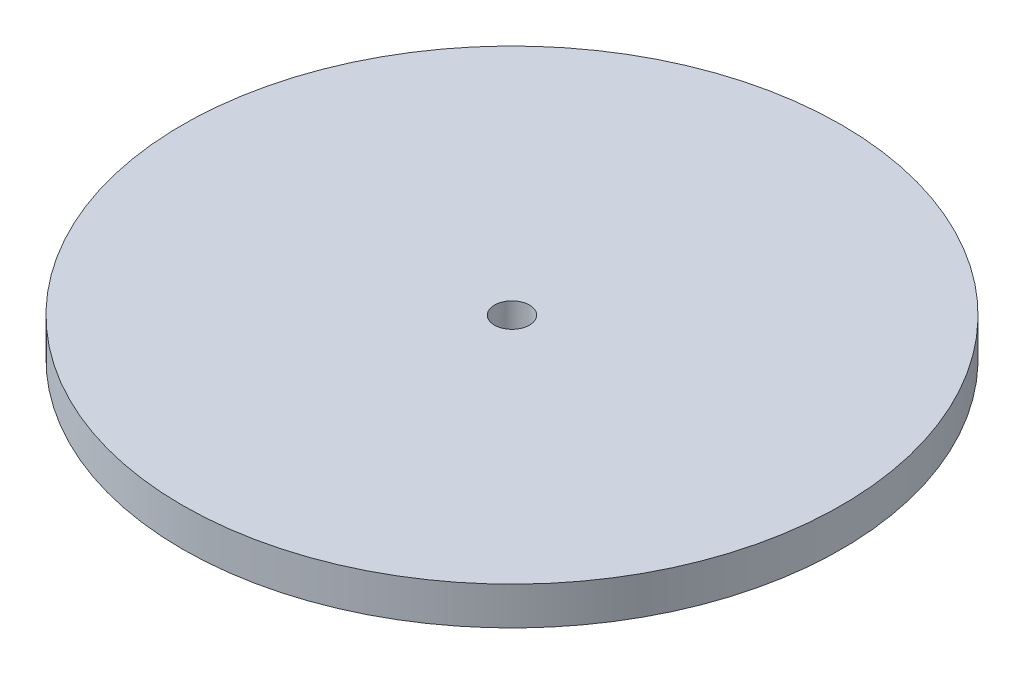
SolidWorks part; units mm, degrees
ref_plane "Front Plane" through (0, 0, 0) normal (0, 0, 1) x (1, 0, 0)
ref_plane "Top Plane" through (0, 0, 0) normal (0, 1, 0) x (1, 0, 0)
ref_plane "Right Plane" through (0, 0, 0) normal (1, 0, 0) x (0, 0, -1)
sketch "Sketch1" plane through (0, 0, 0) normal (0, 1, 0) x (1, 0, 0)
  circle A0 centre (0, 0) radius 83.82
  dimension "D1" = 167.64
extrude "Boss-Extrude1" add sketch "Sketch1" along normal mid plane 9.652
sketch "Sketch2" plane through (0, 0, 0) normal (0, 0, 1) x (1, 0, 0)
  line L0 (0, -18.3275) -> (0, 20.8308) construction
  line L1 (0, -4.826) -> (-19.297, -4.826)
  line L2 (-83.82, -4.826) -> (83.82, -4.826) construction
  line L3 (0, -4.826) -> (0, -1.4952)
  line L4 (-0.3818, -1.4952) -> (0, -1.4952)
  arc A0 (-19.297, -4.826) -> (-0.3818, -1.4952) centre (-0.4072, -56.7254) cw
  dimension "D6" = 55.2302
  dimension "D1" = 19.297
  dimension "D2" = 3.3308
  dimension "D3" = 0.3818
revolve "Cut-Revolve1" cut sketch "Sketch2" angle 360 about L0
sketch "Sketch3" plane through (0, 4.826, 0) normal (0, 1, 0) x (1, 0, 0)
  circle A0 centre (0, 0) radius 4.445
  dimension "D1" = 8.89
extrude "Cut-Extrude1" cut sketch "Sketch3" against normal up to surface (9.652 mm away) up to face at (0, -4.826, -19.297)
